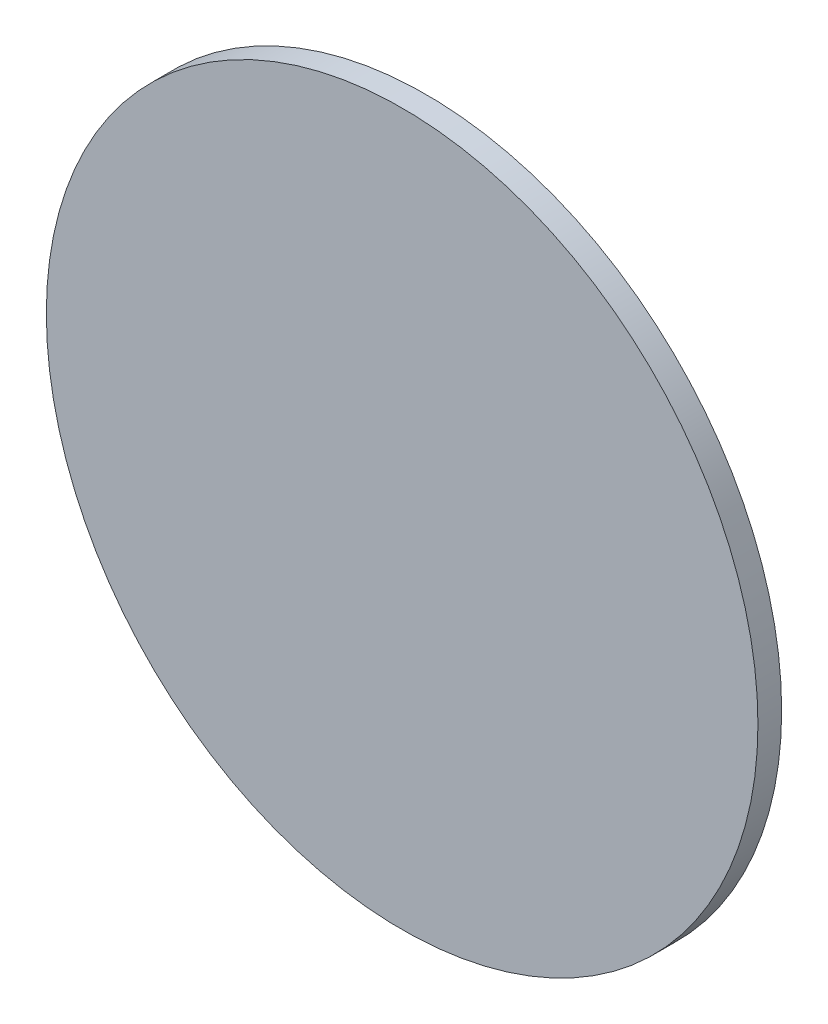
SolidWorks part; units mm, degrees
ref_plane "Front Plane" through (0, 0, 0) normal (0, 0, 1) x (1, 0, 0)
ref_plane "Top Plane" through (0, 0, 0) normal (0, 1, 0) x (1, 0, 0)
ref_plane "Right Plane" through (0, 0, 0) normal (1, 0, 0) x (0, 0, -1)
sketch "Sketch2" plane through (0, 0, 0) normal (0, 0, 1) x (1, 0, 0)
  circle A0 centre (0, 0) radius 30
  dimension "D1" = 60
extrude "Boss-Extrude1" add sketch "Sketch2" along normal blind 2
